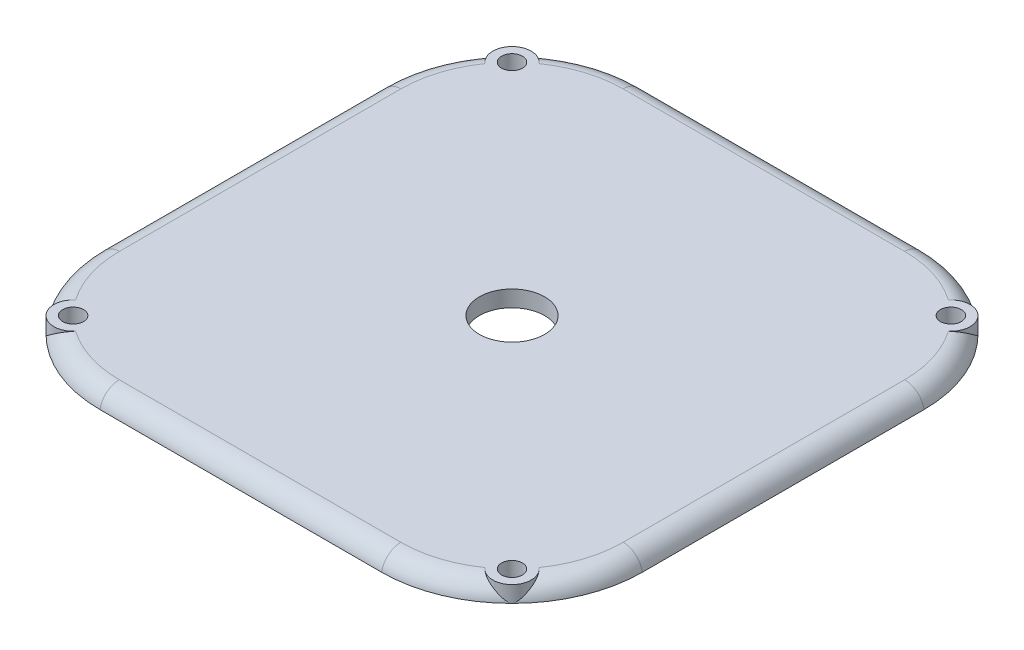
SolidWorks part; units mm, degrees
ref_plane "Front Plane" through (0, 0, 0) normal (0, 0, 1) x (1, 0, 0)
ref_plane "Top Plane" through (0, 0, 0) normal (0, 1, 0) x (1, 0, 0)
ref_plane "Right Plane" through (0, 0, 0) normal (1, 0, 0) x (0, 0, -1)
sketch "Sketch1" plane through (0, 0, 0) normal (0, 1, 0) x (1, 0, 0)
  line L1 (-44.4167, 38.4583) -> (38.7833, 38.4583)
  line L2 (-44.4167, 38.4583) -> (-44.4167, -44.7417)
  line L3 (-44.4167, -44.7417) -> (38.7833, -44.7417)
  line L4 (38.7833, 38.4583) -> (38.7833, -44.7417)
  dimension "D1" = 83.2
  dimension "D2" = 83.2
extrude "Boss-Extrude1" add sketch "Sketch1" along normal blind 2.5
fillet "Fillet1" radius 20 4 edges at (-44.4167, 1.25, -38.4583) (38.7833, 1.25, -38.4583) (38.7833, 1.25, 44.7417) (-44.4167, 1.25, 44.7417)
fillet "Fillet2" radius 3 8 edges at (32.9255, 2.5, -32.6005) (38.7833, 2.5, 3.1417) (32.9255, 2.5, 38.8838) (-2.8167, 2.5, 44.7417) (-38.5588, 2.5, 38.8838) (-44.4167, 2.5, 3.1417) (-38.5588, 2.5, -32.6005) (-2.8167, 2.5, -38.4583)
sketch "Sketch2" plane through (0, 2.5, 0) normal (0, 1, 0) x (1, 0, 0)
  line L0 (18.7833, 35.5003) -> (-24.4167, 35.5003) construction
  line L1 (-41.4586, 18.4583) -> (-41.4586, -24.7417) construction
  circle A0 centre (-36.4786, 30.5203) radius 1.6
  circle A1 centre (-2.8167, -3.1417) radius 10.0525
  circle A2 centre (30.8453, 30.5203) radius 1.6
  circle A3 centre (30.8453, -36.8036) radius 1.6
  circle A4 centre (-36.4786, -36.8036) radius 1.6
  point P17 (-2.8167, -3.1417)
  dimension "D1" = 4.98
  dimension "D2" = 4.98
  dimension "D3" = 3.2
  dimension "D4" = 4
extrude "Cut-Extrude1" cut sketch "Sketch2" against normal blind 5 contours A2 | A0 | A4 | A3
sketch "Sketch4" plane through (0, 0, 0) normal (0, -1, 0) x (1, 0, 0)
  circle A0 centre (-2.8167, 3.1417) radius 11.3267
  circle A1 centre (-36.4786, 36.8036) radius 1.6
  circle A2 centre (-36.4786, 36.8036) radius 2.9418
  circle A3 centre (30.8453, 36.8036) radius 2.9418
  circle A4 centre (30.8453, 36.8036) radius 1.6
  circle A5 centre (30.8453, -30.5203) radius 2.9418
  circle A6 centre (30.8453, -30.5203) radius 1.6
  circle A7 centre (-36.4786, -30.5203) radius 2.9418
  circle A8 centre (-36.4786, -30.5203) radius 1.6
  point P18 (-2.8167, 3.1417)
  dimension "D1" = 4
extrude "Boss-Extrude2" add sketch "Sketch4" against normal up to surface (2.5 mm away) contours A5 | A6 | A7 | A8 | A2 | A1 | A3 | A4 up to face at (-2.8167, 2.5, 3.1417)
sketch "Sketch5" plane through (0, 2.5, 0) normal (0, 1, 0) x (1, 0, 0)
  circle A0 centre (-2.8167, -3.1417) radius 5
  dimension "D1" = 10
extrude "Cut-Extrude2" cut sketch "Sketch5" against normal blind 5
